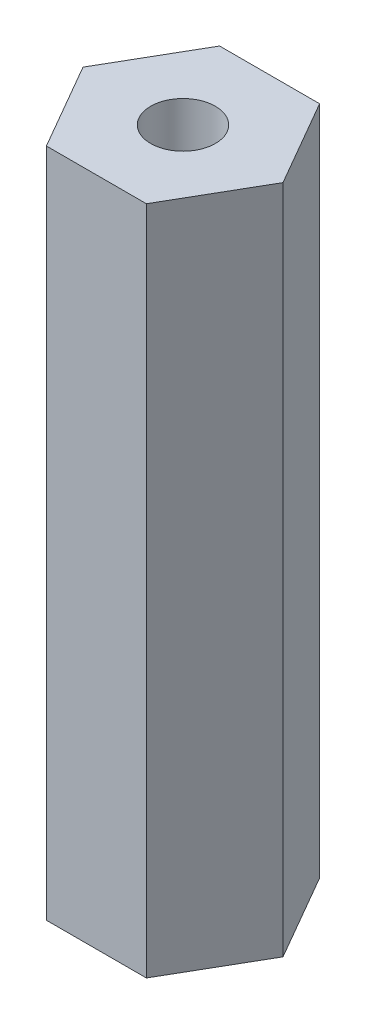
SolidWorks part; units mm, degrees
material "Brass"
ref_plane "Front Plane" through (0, 0, 0) normal (0, 0, 1) x (1, 0, 0)
ref_plane "Top Plane" through (0, 0, 0) normal (0, 1, 0) x (1, 0, 0)
ref_plane "Right Plane" through (0, 0, 0) normal (1, 0, 0) x (0, 0, -1)
sketch "Sketch1" plane through (0, 0, 0) normal (0, 1, 0) x (1, 0, 0)
  line L1 (4.3994, 0) -> (2.1997, 3.81)
  line L2 (2.1997, 3.81) -> (-2.1997, 3.81)
  line L3 (-2.1997, 3.81) -> (-4.3994, 0)
  line L4 (-4.3994, 0) -> (-2.1997, -3.81)
  line L5 (-2.1997, -3.81) -> (2.1997, -3.81)
  line L6 (2.1997, -3.81) -> (4.3994, 0)
  circle A0 centre (0, 0) radius 3.81 construction
extrude "Boss-Extrude1" add sketch "Sketch1" along normal blind 29.5
sketch "Sketch2" plane through (0, 0, 0) normal (0, -1, 0) x (-1, 0, 0)
  circle A0 centre (0, 0) radius 1.4224
  dimension "D1" = 2.8448
extrude "Cut-Extrude1" cut sketch "Sketch2" against normal through all
equation "\"D1@Boss-Extrude1\"=29.5mm"
equation "\"D1@Sketch2\"=.112"
